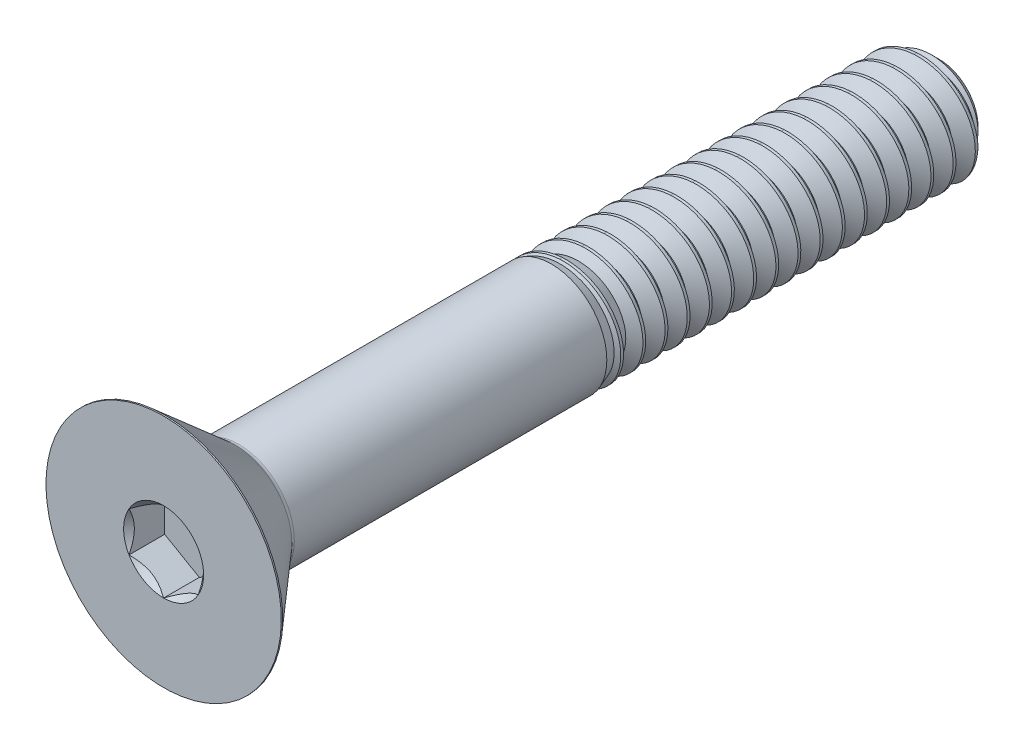
SolidWorks part; units mm, degrees
ref_plane "Front Plane" through (0, 0, 0) normal (0, 0, 1) x (1, 0, 0)
ref_plane "Top Plane" through (0, 0, 0) normal (0, 1, 0) x (1, 0, 0)
ref_plane "Right Plane" through (0, 0, 0) normal (1, 0, 0) x (0, 0, -1)
sketch "Sketch1" plane through (0, 0, 0) normal (1, 0, 0) x (0, 0, -1)
  line L0 (-22.225, 0) -> (22.225, 0) construction
  line L1 (-22.225, 0) -> (-22.225, 6.7437)
  line L2 (-22.225, 6.7437) -> (-22.1432, 6.7437)
  line L3 (-22.1432, 6.7437) -> (-18.1356, 3.2599)
  line L4 (-22.1432, -6.7437) -> (-18.1356, -3.2599)
  line L5 (22.225, 0) -> (22.225, 3.175)
  line L6 (22.225, 3.175) -> (-18.1356, 3.175)
  line L7 (21.2725, 3.175) -> (22.225, 2.2225)
  line L8 (22.1456, 3.3125) -> (22.7806, 2.2126) construction
  line L9 (22.7806, 2.2126) -> (23.4156, 3.3125) construction
  line L10 (23.4156, 3.3125) -> (22.1456, 3.3125) construction
  line L11 (22.1853, 3.2437) -> (23.3759, 3.2437)
  line L12 (23.3759, 3.2437) -> (22.86, 2.3501)
  line L13 (22.86, 2.3501) -> (22.7013, 2.3501)
  line L14 (22.7013, 2.3501) -> (22.1853, 3.2437)
  line L15 (22.7806, 2.3501) -> (22.7806, 2.2126) construction
  line L16 (22.225, 3.175) -> (23.3363, 3.175) construction
  line L17 (22.7806, 3.3125) -> (22.7806, 3.175) construction
  line L18 (22.225, -3.175) -> (-18.1356, -3.175)
  arc A0 (-18.1356, 3.2599) -> (-17.9084, 3.175) centre (-17.9084, 3.5213) ccw
  point P2 (0, 0)
  point P23 (-20.1803, 0)
  point P27 (22.7806, 3.2437)
  point P29 (-22.1432, -6.7437)
  point P31 (19.05, -3.175)
  point P32 (-12.5793, -6.7437)
  point P33 (-2.2225, -6.7437)
  point P34 (-15.9131, -6.7437)
  point P35 (0, 3.175)
  dimension "Length" = 44.45
  dimension "Head Height" = 4.0894
  dimension "Head Diameter" = 13.4874
  dimension "Countersink Angle" = 82
  dimension "Screw Size Decimal Equivalent" = 6.35
  dimension "Pitch" = 1.27
  dimension "D4" = 0.1588
  dimension "D3" = 45
  dimension "D5" = 0.9525
  dimension "D6" = 2.0447
  dimension "D1" = 3.175
  dimension "Minimum Thread Length" = 22.225
  dimension "D8" = 2.2225
  dimension "D7" = 2.2225
  dimension "D9" = 5.5562
  dimension "D2" = 0.0818
sketch "Sketch8" plane through (0, 0, 0) normal (0, 0, 1) x (1, 0, 0)
  line L1 (0, 2.2914) -> (-1.9844, 1.1457)
  line L2 (-1.9844, 1.1457) -> (-1.9844, -1.1457)
  line L3 (-1.9844, -1.1457) -> (0, -2.2914)
  line L4 (0, -2.2914) -> (1.9844, -1.1457)
  line L5 (1.9844, -1.1457) -> (1.9844, 1.1457)
  line L6 (1.9844, 1.1457) -> (0, 2.2914)
  circle A0 centre (0, 0) radius 1.9844 construction
  dimension "Drive Size" = 3.9688
sketch "Sketch2" plane through (0, 0, 0) normal (1, 0, 0) x (0, 0, -1)
  line L0 (-22.1432, 6.7437) -> (-18.1356, 3.2599) construction
  line L1 (-22.225, 0) -> (-22.225, 6.7437) construction
  line L2 (-22.1432, 6.7437) -> (-18.1356, 3.2599)
  line L3 (-22.225, 0) -> (-22.225, 6.7437)
  line L4 (-22.225, 6.7437) -> (-22.1432, 6.7437) construction
  line L5 (-22.225, 6.7437) -> (-22.1432, 6.7437)
  line L6 (-17.9084, 3.175) -> (21.2725, 3.175)
  line L7 (21.2725, 3.175) -> (22.225, 2.2225)
  line L8 (22.225, 2.2225) -> (22.225, 0)
  line L9 (22.225, 0) -> (-22.225, 0)
  arc A0 (-18.1356, 3.2599) -> (-17.9084, 3.175) centre (-17.9084, 3.5213) ccw construction
  arc A1 (-18.1356, 3.2599) -> (-17.9084, 3.175) centre (-17.9084, 3.5213) ccw
revolve "Revolve1" add sketch "Sketch2" angle 360 about L9
sketch "Sketch9" plane through (0, 0, 22.225) normal (0, 0, 1) x (1, 0, 0)
  line L0 (1.9844, -1.1457) -> (1.9844, 1.1457) construction
  line L1 (0, -2.2914) -> (1.9844, -1.1457) construction
  line L2 (-1.9844, -1.1457) -> (0, -2.2914) construction
  line L3 (-1.9844, 1.1457) -> (-1.9844, -1.1457) construction
  line L4 (0, 2.2914) -> (-1.9844, 1.1457) construction
  line L5 (1.9844, 1.1457) -> (0, 2.2914) construction
  line L6 (1.9844, -1.1457) -> (1.9844, 1.1457)
  line L7 (0, -2.2914) -> (1.9844, -1.1457)
  line L8 (-1.9844, -1.1457) -> (0, -2.2914)
  line L9 (-1.9844, 1.1457) -> (-1.9844, -1.1457)
  line L10 (0, 2.2914) -> (-1.9844, 1.1457)
  line L11 (1.9844, 1.1457) -> (0, 2.2914)
sketch "Sketch10" plane through (0, 0, 22.225) normal (0, 0, 1) x (1, 0, 0)
  circle A0 centre (0, 0) radius 2.2914
extrude "Cut-Extrude2" cut sketch "Sketch10" against normal up to vertex (2.0447 mm away) draft 45 up to point (0, 0, 20.1803)
extrude "Cut-Extrude1" cut sketch "Sketch9" against normal up to vertex (2.0447 mm away) up to point (0, 0, 20.1803)
ref_plane "Plane1" through (0, 0, 0) normal (0, 0, 1) x (1, 0, 0)
split "Split1" trim tools "Plane1" bodies to split 111 resulting bodies 105 106
sketch "Sketch3" plane through (0, 0, -22.225) normal (0, 0, -1) x (-1, 0, 0)
  circle A0 centre (0, 0) radius 3.175 construction
  circle A1 centre (0, 0) radius 3.175
curve "Helix/Spiral1" pitch 1.27 height 23.495 turns 18.5
sketch "Sketch4" plane through (0, 0, 0) normal (1, 0, 0) x (0, 0, -1)
  line L0 (22.1853, 3.2437) -> (23.3759, 3.2437) construction
  line L1 (22.7013, 2.3501) -> (22.1853, 3.2437) construction
  line L2 (22.86, 2.3501) -> (22.7013, 2.3501) construction
  line L3 (23.3759, 3.2437) -> (22.86, 2.3501) construction
  line L4 (22.1853, 3.2437) -> (23.3759, 3.2437)
  line L5 (22.7013, 2.3501) -> (22.1853, 3.2437)
  line L6 (22.86, 2.3501) -> (22.7013, 2.3501)
  line L7 (23.3759, 3.2437) -> (22.86, 2.3501)
sweep "Cut-Sweep3" cut profiles "Sketch4" path "Helix/Spiral1"
sketch "Sketch11" plane through (0, 0, 0) normal (0, 0, 1) x (1, 0, 0)
  circle A0 centre (0, 0) radius 3.175
extrude "Boss-Extrude1" add sketch "Sketch11" against normal up to next (22.225 mm away) draft 20
equation "\"D4@Sketch1\" = \"Pitch@Sketch1\" / 8"
equation "\"D5@Sketch1\"=\"Pitch@Sketch1\"*0.75"
equation "\"D4@Helix/Spiral1\"=\"Pitch@Sketch1\""
equation "\"D3@Helix/Spiral1\"=\"Minimum Thread Length@Sketch1\"+\"Pitch@Sketch1\""
equation "\"D6@Sketch1\"=\"Head Height@Sketch1\"/2"
equation "\"D1@Sketch1\"=\"Pitch@Sketch1\"*2.5"
equation "\"D8@Sketch1\"=\"Length@Sketch1\"*0.05"
equation "\"D7@Sketch1\"=\"D8@Sketch1\""
equation "\"D9@Sketch1\"=2.5*\"D7@Sketch1\""
